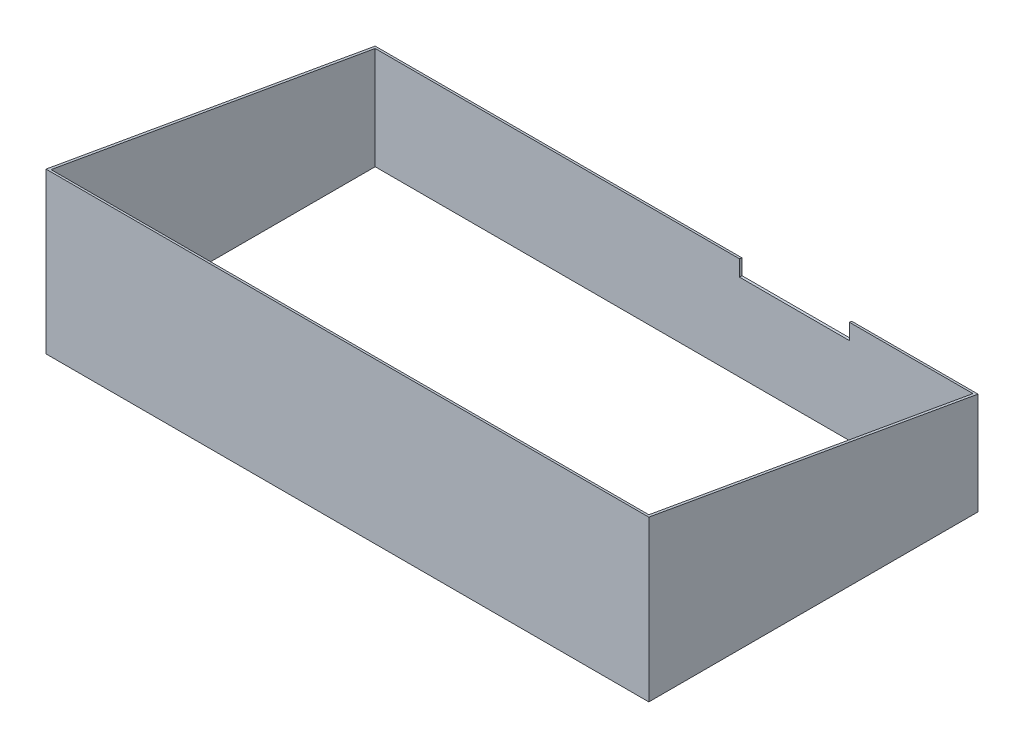
SolidWorks part; units mm, degrees
material "Particle Board"
ref_plane "Front Plane" through (0, 0, 0) normal (0, 0, 1) x (1, 0, 0)
ref_plane "Top Plane" through (0, 0, 0) normal (0, 1, 0) x (1, 0, 0)
ref_plane "Right Plane" through (0, 0, 0) normal (1, 0, 0) x (0, 0, -1)
sketch "Sketch1" plane through (0, 0, 0) normal (1, 0, 0) x (0, 0, -1)
  line L0 (0, 403.2291) -> (0, 0)
  line L1 (0, 0) -> (829.3066, 0)
  line L4 (829.3066, 0) -> (829.3066, 257)
  line L5 (0, 403.2291) -> (829.3066, 257)
  dimension "D1" = 10
  dimension "D2" = 842.1
  dimension "D3" = 257
extrude "Boss-Extrude1" add sketch "Sketch1" along normal blind 759.38 and the other way blind 759.38
shell "Shell1" thickness 6.35 removed face at (0, 0, -414.6533) removed face at (0, 330.1146, -414.6533)
sketch "Sketch3" plane through (0, 0, -822.9566) normal (0, 0, 1) x (1, 0, 0)
  line L1 (164.73, 268.1197) -> (441.73, 268.1197)
  line L2 (164.73, 268.1197) -> (164.73, 218.1197)
  line L3 (164.73, 218.1197) -> (441.73, 218.1197)
  line L4 (441.73, 268.1197) -> (441.73, 218.1197)
  line L5 (753.03, 258.1197) -> (-753.03, 258.1197) construction
  line L7 (0, -221.776) -> (0, 221.776) construction
  dimension "D1" = 164.73
  dimension "D2" = 277
  dimension "D3" = 10
  dimension "D4" = 40
extrude "Cut-Extrude2" cut sketch "Sketch3" against normal up to next
